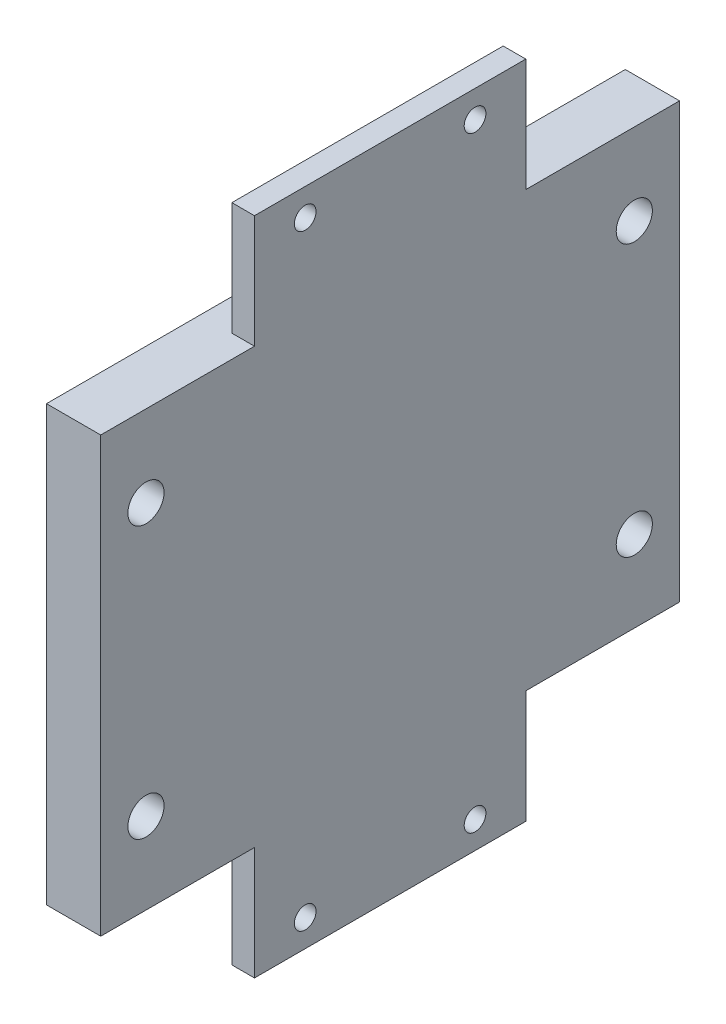
SolidWorks part; units mm, degrees
ref_plane "前视基准面" through (0, 0, 0) normal (0, 0, 1) x (1, 0, 0)
ref_plane "上视基准面" through (0, 0, 0) normal (0, 1, 0) x (1, 0, 0)
ref_plane "右视基准面" through (0, 0, 0) normal (1, 0, 0) x (0, 0, -1)
other "Configuration Table"
sketch "草图1" plane through (0, 0, 0) normal (1, 0, 0) x (0, 0, -1)
  line L5 (-16, -12) -> (16, -12)
  line L6 (-16, -12) -> (-16, 12)
  line L7 (-16, 12) -> (16, 12)
  line L8 (16, -12) -> (16, 12)
  line L9 (-16, -12) -> (16, 12) construction
  line L10 (-16, 12) -> (16, -12) construction
  point P0 (0, 0)
  point P2 (0, 0)
  point P6 (0, 0)
  point P7 (0, 0)
  dimension "D1" = 32
  dimension "D3" = 24
extrude "凸台-拉伸1" add sketch "草图1" along normal blind 3
sketch "草图4" plane through (0, 0, 0) normal (-1, 0, 0) x (0, 0, 1)
  line L0 (-16, 12) -> (16, 12) construction
  line L1 (3.2, 12) -> (-3.2, 12)
  line L2 (3.2, 12) -> (3.2, -12)
  line L3 (3.2, -12) -> (-3.2, -12)
  line L4 (-3.2, 12) -> (-3.2, -12)
  line L5 (16, -12) -> (-16, -12) construction
  line L6 (0, 12) -> (0, 0) construction
  point P10 (0, 0)
  dimension "D1" = 6.4
extrude "切除-拉伸1" cut sketch "草图4" against normal blind 1.75
sketch "草图5" plane through (0, -12, 0) normal (0, -1, 0) x (1, 0, 0)
  line L0 (3, 16) -> (3, -16) construction
  line L1 (3, 7.5) -> (1.75, 7.5)
  line L2 (3, 7.5) -> (3, -7.5)
  line L3 (3, -7.5) -> (1.75, -7.5)
  line L4 (1.75, 7.5) -> (1.75, -7.5)
  line L5 (0, 0) -> (1.75, 0) construction
  point P6 (0, 0)
  point P7 (1.75, 7.8262)
  point P8 (1.7615, -7.7929)
  point P12 (1.7503, -7.826)
  point P13 (1.75, -7.8262)
  dimension "D1" = 1.25
  dimension "D2" = 15
extrude "凸台-拉伸2" add sketch "草图5" along normal blind 6.25
extrude "凸台-拉伸3" add sketch "草图5<2>" against normal blind 6.25 from surface starting at face at (1.1875, 12, 0)
sketch "草图5<2>" plane through (0, -12, 0) normal (0, -1, 0) x (1, 0, 0) same geometry as "草图5"
sketch "草图6" plane through (3, 0, 0) normal (1, 0, 0) x (0, 0, -1)
  circle A0 centre (4.6957, -16.75) radius 0.6
  circle A1 centre (4.6957, -16.75) radius 1
  circle A2 centre (-4.6957, -16.75) radius 1
  circle A3 centre (-4.6957, -16.75) radius 0.6
  circle A4 centre (4.6957, 16.75) radius 1
  circle A5 centre (4.6957, 16.75) radius 0.6
  circle A6 centre (-4.6957, 16.75) radius 1
  circle A7 centre (-4.6957, 16.75) radius 0.6
  point P12 (0, 0)
  dimension "D1" = 1.2
  dimension "D2" = 2
extrude "切除-拉伸2" cut sketch "草图6" against normal through all contours A0 | A3 | A7 | A5
sketch "草图7" plane through (0, 0, 0) normal (-1, 0, 0) x (0, 0, 1)
  line L0 (13.5, 7.5) -> (-13.5, -7.5) construction
  line L1 (-13.5, 7.5) -> (13.5, -7.5) construction
  circle A0 centre (13.5, 7.5) radius 1.75
  circle A1 centre (13.5, -7.5) radius 1.75
  circle A2 centre (-13.5, 7.5) radius 1.75
  circle A3 centre (-13.5, -7.5) radius 1.75
  circle A4 centre (13.5, 7.5) radius 1
  circle A5 centre (13.5, -7.5) radius 1
  circle A6 centre (-13.5, -7.5) radius 1
  circle A7 centre (-13.5, 7.5) radius 1
  point P12 (0, 0)
  point P13 (0, 0)
  dimension "D1" = 2
  dimension "D2" = 3.5
  dimension "D3" = 15
  dimension "D4" = 27
extrude "切除-拉伸4" cut sketch "草图7" against normal blind 1.5
extrude "切除-拉伸5" cut sketch "草图7<2>" against normal through all contours A5 | A4 | A7 | A6
sketch "草图7<2>" plane through (0, 0, 0) normal (-1, 0, 0) x (0, 0, 1) same geometry as "草图7"
